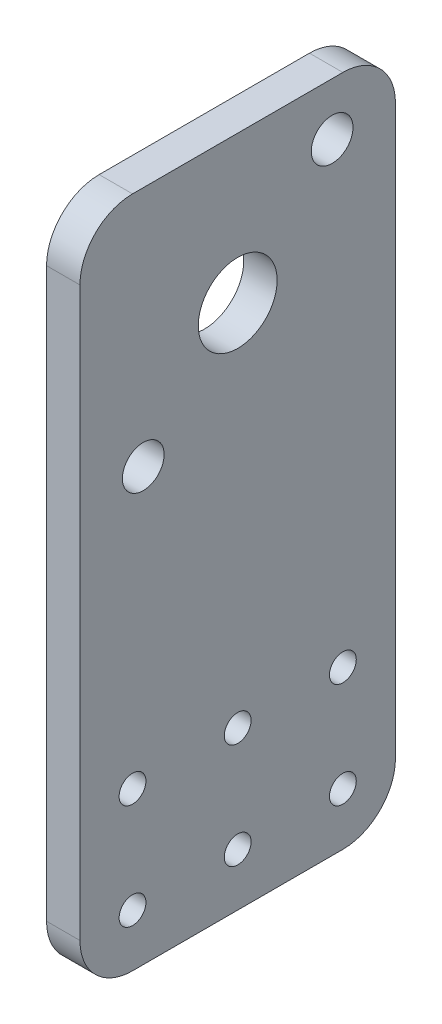
SolidWorks part; units mm, degrees
ref_plane "Front Plane" through (0, 0, 0) normal (0, 0, 1) x (1, 0, 0)
ref_plane "Top Plane" through (0, 0, 0) normal (0, 1, 0) x (1, 0, 0)
ref_plane "Right Plane" through (0, 0, 0) normal (1, 0, 0) x (0, 0, -1)
sketch "Sketch1" plane through (0, 0, 0) normal (1, 0, 0) x (0, 0, -1)
  line L0 (17.9605, 117.9605) -> (-17.9605, 82.0395) construction
  line L1 (-30, 127.9605) -> (30, 127.9605)
  line L2 (-30, 127.9605) -> (-30, 0)
  line L3 (-30, 0) -> (30, 0)
  line L4 (30, 127.9605) -> (30, 0)
  line L5 (-30, 40) -> (30, 40) construction
  line L6 (-20, 30) -> (0, 30) construction
  circle A0 centre (0, 100) radius 7.5
  circle A1 centre (17.9605, 117.9605) radius 3.9688
  circle A2 centre (-17.9605, 82.0395) radius 3.9688
  circle A3 centre (-20, 30) radius 2.55
  circle A4 centre (0, 30) radius 2.55
  circle A5 centre (20, 30) radius 2.55
  circle A6 centre (0, 10) radius 2.55
  circle A7 centre (20, 10) radius 2.55
  circle A8 centre (-20, 10) radius 2.55
  point P6 (0, 0)
  point P14 (0, 0)
  point P15 (27.9605, 119.5163)
  point P16 (0, 127.9605)
  point P17 (17.9605, 113.6586)
  point P32 (20, 13.3565)
  dimension "D2" = 15
  dimension "D9" = 5.1
  dimension "D16" = 7.9375
  dimension "D4" = 50.8
  dimension "D5" = 10
  dimension "D6" = 40
  dimension "D7" = 10
  dimension "D8" = 10
  dimension "D12" = 20
  dimension "D13" = 45
  dimension "D3" = 10
  dimension "D14" = 10
  dimension "D15" = 100
  dimension "D17" = 10
  dimension "D10" = 3
  dimension "D11" = 2
extrude "Boss-Extrude1" add sketch "Sketch1" along normal blind 6.35
fillet "Fillet1" radius 10 4 edges at (3.175, 0, 30) (3.175, 0, -30) (3.175, 127.9605, -30) (3.175, 127.9605, 30)
equation "\"D14@Sketch1\"=\"D3@Sketch1\""
